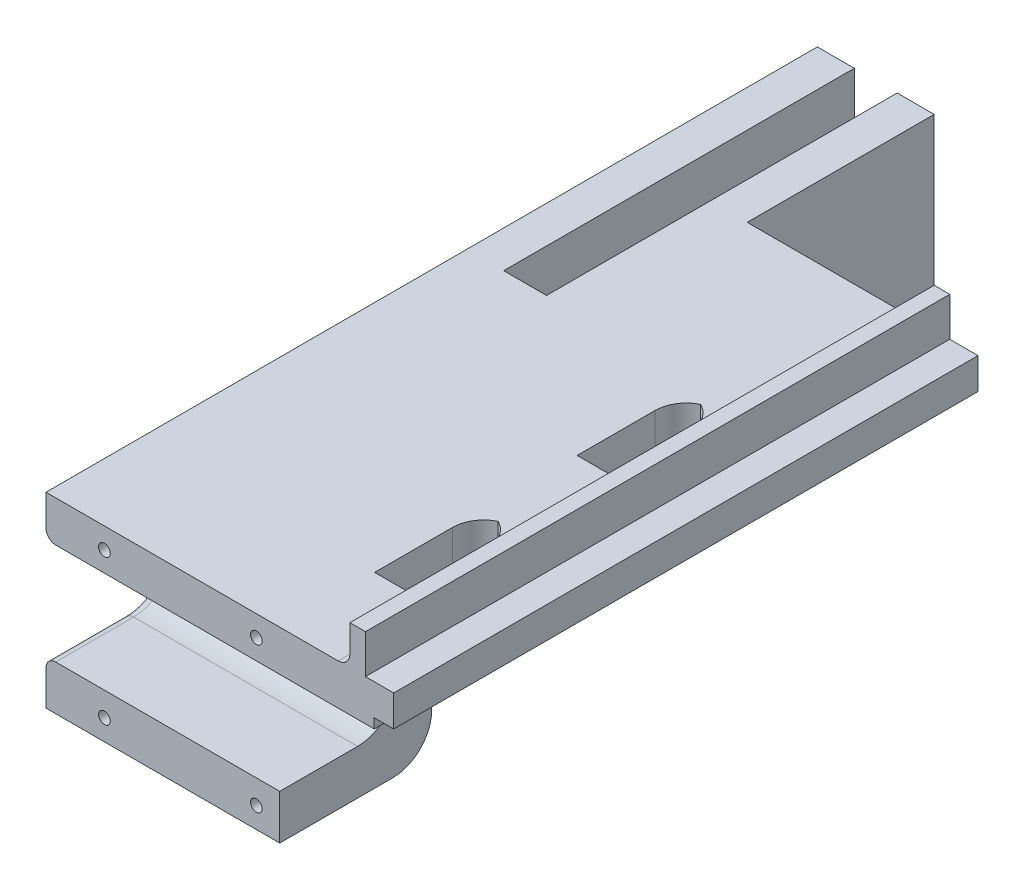
SolidWorks part; units mm, degrees
ref_plane "Alzado" through (0, 0, 0) normal (0, 0, 1) x (1, 0, 0)
ref_plane "Planta" through (0, 0, 0) normal (0, 1, 0) x (1, 0, 0)
ref_plane "Vista lateral" through (0, 0, 0) normal (1, 0, 0) x (0, 0, -1)
sketch "Croquis1" plane through (0, 0, 0) normal (0, 0, 1) x (1, 0, 0)
  line L1 (-66.2162, 31.0113) -> (-6.2162, 31.0113)
  line L2 (-66.2162, 31.0113) -> (-66.2162, -16.9887)
  line L3 (-66.2162, -16.9887) -> (-6.2162, -16.9887)
  line L4 (-6.2162, 31.0113) -> (-6.2162, -16.9887)
  dimension "D1" = 48
  dimension "D2" = 60
extrude "Saliente-Extruir1" add sketch "Croquis1" along normal blind 6
sketch "Croquis4" plane through (0, 0, 6) normal (0, 0, 1) x (1, 0, 0)
  line L0 (-66.2162, 31.0113) -> (-66.2162, 19.5113)
  line L1 (-66.2162, 31.0113) -> (-66.2162, -16.9887) construction
  line L3 (-66.2162, -5.4887) -> (-66.2162, -16.9887)
  line L4 (-66.2162, 31.0113) -> (-6.2162, 31.0113)
  line L6 (-6.2162, 31.0113) -> (-6.2162, 19.5113)
  line L7 (-6.2162, -16.9887) -> (-6.2162, 31.0113) construction
  line L8 (-6.2162, 19.5113) -> (-66.2162, 19.5113)
  line L9 (-66.2162, -5.4887) -> (-6.2162, -5.4887)
  line L10 (-6.2162, -5.4887) -> (-6.2162, -16.9887)
  line L11 (-6.2162, -16.9887) -> (-66.2162, -16.9887)
  dimension "D1" = 25
extrude "Saliente-Extruir3" add sketch "Croquis4" along normal blind 30
sketch "Croquis3" plane through (0, 0, 6) normal (0, 0, 1) x (1, 0, 0)
  circle A0 centre (-51.2162, 25.6613) radius 2.125
  circle A1 centre (-12.2162, 25.6613) radius 2.125
  circle A2 centre (-12.2162, -11.6387) radius 2.125
  circle A3 centre (-51.2162, -11.6387) radius 2.125
  dimension "D7" = 4.25
  dimension "D9" = 4.25
  dimension "D10" = 4.25
  dimension "D2" = 4.25
  dimension "D3" = 37.3
  dimension "D4" = 39
sketch "Croquis5" plane through (0, 0, 36) normal (0, 0, 1) x (1, 0, 0)
  circle A0 centre (-51.2162, 25.6613) radius 1.5
  circle A1 centre (-12.2162, 25.6613) radius 1.5
  circle A2 centre (-12.2162, -11.6387) radius 1.5
  circle A3 centre (-51.2162, -11.6387) radius 1.5
  dimension "D1" = 3
  dimension "D2" = 3
  dimension "D3" = 3
  dimension "D4" = 3
extrude "Cortar-Extruir3" cut sketch "Croquis5" against normal blind 16
sketch "Croquis6" plane through (0, 0, 0) normal (0, 0, -1) x (-1, 0, 0)
  line L0 (66.2162, -16.9887) -> (6.2162, -16.9887) construction
  line L1 (66.2162, 31.0113) -> (36.2162, 31.0113)
  line L2 (66.2162, 31.0113) -> (66.2162, -16.9887)
  line L3 (66.2162, -16.9887) -> (36.2162, -16.9887)
  line L4 (36.2162, 31.0113) -> (36.2162, -16.9887)
  dimension "D1" = 30
extrude "Saliente-Extruir4" add sketch "Croquis6" along normal blind 162
sketch "Croquis7" plane through (0, 0, -162) normal (0, 0, -1) x (-1, 0, 0)
  circle A0 centre (51.2162, 7.0113) radius 2
  dimension "D1" = 4
extrude "Cortar-Extruir4" cut sketch "Croquis7" against normal blind 16
sketch "Croquis8" plane through (0, 0, -162) normal (0, 0, -1) x (-1, 0, 0)
  line L0 (41.2162, 12.0113) -> (41.2162, 9.5131)
  line L10 (36.2162, 12.0113) -> (41.2162, 12.0113)
  line L11 (36.2162, 12.0113) -> (36.2162, 2.0113)
  line L12 (36.2162, 2.0113) -> (41.2162, 2.0113)
  line L21 (41.2162, 9.5131) -> (44.2162, 9.5131)
  line L23 (41.2162, 4.5131) -> (44.2162, 4.5131)
  line L24 (44.2162, 9.5131) -> (44.2162, 4.5131)
  line L25 (41.2162, 2.0113) -> (41.2162, 4.5131)
  dimension "D1" = 5
  dimension "D2" = 3
  dimension "D3" = 5
sketch "Croquis11" plane through (-36.2162, 0, 0) normal (1, 0, 0) x (0, 0, -1)
  line L1 (-36, 19.5113) -> (-36, 31.0113) construction
  line L4 (-36, 19.5113) -> (-36, 31.0113)
  line L6 (-36, 19.5113) -> (114, 19.5113)
  line L7 (114, 19.5113) -> (114, 31.0113)
  line L8 (162, 31.0113) -> (0, 31.0113) construction
  line L9 (162, 31.0113) -> (0, 31.0113) construction
  line L10 (-36, 31.0113) -> (114, 31.0113)
  dimension "D1" = 150
extrude "Saliente-Extruir6" add sketch "Croquis11" along normal blind 59.25
sketch "Croquis12" plane through (0, 31.0113, 0) normal (0, 1, 0) x (1, 0, 0)
  line L0 (23.0338, -36) -> (-66.2162, -36) construction
  line L1 (15.7838, -36) -> (11.7838, -36)
  line L2 (-66.2162, -36) -> (-66.2162, 162) construction
  line L3 (-66.2162, -36) -> (-66.2162, 162) construction
  line L4 (15.7838, -36) -> (15.7838, 114)
  line L5 (15.7838, 114) -> (11.7838, 114)
  line L6 (23.0338, 114) -> (-36.2162, 114) construction
  line L7 (11.7838, 114) -> (11.7838, -36)
  dimension "D1" = 82
  dimension "D2" = 150
  dimension "D3" = 4
extrude "Saliente-Extruir7" add sketch "Croquis12" along normal blind 10
sketch "Croquis14" plane through (0, 0, -114) normal (0, 0, -1) x (-1, 0, 0)
  line L0 (-23.0338, 23.0113) -> (-18.0338, 23.0113)
  line L1 (-18.0338, 23.0113) -> (-18.0338, 19.5113)
  line L2 (-23.0338, 23.0113) -> (-23.0338, 19.5113)
  line L3 (-23.0338, 19.5113) -> (-18.0338, 19.5113)
  line L4 (36.2162, 19.5113) -> (36.2162, 31.0113)
  line L5 (36.2162, 31.0113) -> (-11.7838, 31.0113)
  line L6 (-23.0338, 31.0113) -> (-23.0338, 19.5113)
  line L7 (-23.0338, 19.5113) -> (36.2162, 19.5113)
  line L8 (36.2162, 19.5113) -> (36.2162, 31.0113) construction
  line L9 (36.2162, 31.0113) -> (-11.7838, 31.0113) construction
  line L10 (-23.0338, 31.0113) -> (-23.0338, 19.5113) construction
  line L11 (-23.0338, 19.5113) -> (36.2162, 19.5113) construction
  line L20 (-11.7838, 31.0113) -> (-11.7838, 41.0113)
  line L22 (-11.7838, 41.0113) -> (-15.7838, 41.0113)
  line L24 (-15.7838, 41.0113) -> (-15.7838, 31.0113)
  line L26 (-15.7838, 31.0113) -> (-23.0338, 31.0113)
  line L27 (-15.7838, 31.0113) -> (-23.0338, 31.0113) construction
  dimension "D2" = 5
  dimension "D3" = 8
  dimension "D1" = 0
extrude "Cortar-Extruir6" cut sketch "Croquis14" against normal through all both and the other way through all
sketch "Croquis15" plane through (0, 0, -162) normal (0, 0, -1) x (-1, 0, 0)
  line L0 (51.2162, 45.0729) -> (51.2162, 16.9496) construction
  line L1 (56.7162, 20.0113) -> (45.7162, 20.0113)
  line L2 (45.7162, 20.0113) -> (45.7162, 31.0113)
  line L3 (56.7162, 20.0113) -> (56.7162, 31.0113)
  line L4 (66.2162, -16.9887) -> (66.2162, 31.0113)
  line L5 (66.2162, 31.0113) -> (36.2162, 31.0113)
  line L6 (36.2162, 31.0113) -> (36.2162, -16.9887)
  line L7 (36.2162, -16.9887) -> (66.2162, -16.9887)
  line L8 (66.2162, -16.9887) -> (66.2162, 31.0113) construction
  line L9 (66.2162, 31.0113) -> (36.2162, 31.0113) construction
  line L10 (56.7162, 31.0113) -> (45.7162, 31.0113)
  point P6 (51.2162, 31.0113)
  point P10 (51.2162, 20.0113)
  dimension "D2" = 11
  dimension "D3" = 11
  dimension "D1" = 0
extrude "Cortar-Extruir7" cut sketch "Croquis15" against normal blind 90 and the other way through all
sketch "Croquis16" plane through (-66.2162, 0, 0) normal (-1, 0, 0) x (0, 0, 1)
  line L0 (6, 19.5113) -> (6, 20.5113)
  line L1 (6, 20.5113) -> (36, 20.5113)
  line L2 (36, 31.0113) -> (36, 19.5113) construction
  line L3 (6, 19.5113) -> (36, 19.5113)
  line L4 (36, 19.5113) -> (36, 20.5113)
  dimension "D1" = 1
extrude "Cortar-Extruir10" cut sketch "Croquis16" against normal through all contours L1 L4 L3 L0
fillet "Redondeo1" radius 10 2 edges at (-36.2162, -5.4887, 6) (-24.0912, 20.5113, 6)
sketch "Croquis20" plane through (0, 0, 0) normal (0, 0, -1) x (-1, 0, 0)
  line L1 (6.2162, 19.5113) -> (36.2162, 19.5113)
  line L2 (6.2162, 19.5113) -> (6.2162, -16.9887)
  line L3 (6.2162, -16.9887) -> (36.2162, -16.9887)
  line L4 (36.2162, 19.5113) -> (36.2162, -16.9887)
extrude "Saliente-Extruir8" add sketch "Croquis20" along normal blind 50
sketch "Croquis21" plane through (0, 19.5113, 0) normal (0, -1, 0) x (1, 0, 0)
  line L1 (2.7838, 11.6411) -> (-6.2162, 11.6411)
  line L2 (2.7838, 11.6411) -> (2.7838, -16.3589)
  line L3 (2.7838, -16.3589) -> (-6.2162, -16.3589)
  line L4 (-6.2162, 11.6411) -> (-6.2162, -16.3589)
  line L5 (18.0338, 11.6411) -> (-6.2162, 11.6411) construction
  line L6 (-6.2162, 36) -> (-6.2162, -50) construction
  line L12 (-1.7162, 20.4456) -> (-1.7162, -78.1671) construction
  line L13 (2.7838, -40.3589) -> (2.7838, -68.3589)
  line L14 (2.7838, -40.3589) -> (-6.2162, -40.3589)
  line L15 (-6.2162, -40.3589) -> (-6.2162, -68.3589)
  line L16 (2.7838, -68.3589) -> (-6.2162, -68.3589)
  point P10 (-1.7162, -16.3589)
  dimension "D1" = 9
  dimension "D2" = 28
  dimension "D3" = 2
  dimension "D4" = 24
extrude "Cortar-Extruir11" cut sketch "Croquis21" against normal blind 40
sketch "Croquis22" plane through (0, 0, -50) normal (0, 0, -1) x (-1, 0, 0)
  line L1 (36.2162, 19.5113) -> (6.2162, 19.5113)
  line L2 (36.2162, 19.5113) -> (36.2162, -16.9887)
  line L3 (36.2162, -16.9887) -> (6.2162, -16.9887)
  line L4 (6.2162, 19.5113) -> (6.2162, -16.9887)
extrude "Cortar-Extruir13" cut sketch "Croquis22" against normal blind 47
fillet "Redondeo3" radius 10 1 edges at (-21.2162, -16.9887, -3)
sketch "Croquis23" plane through (0, 0, 36) normal (0, 0, 1) x (1, 0, 0)
  circle A0 centre (-12.2162, -11.6387) radius 1.5 construction
  circle A1 centre (-51.2162, -11.6387) radius 1.5 construction
  circle A2 centre (-12.2162, 25.6613) radius 1.5 construction
  circle A3 centre (-51.2162, 25.6613) radius 1.5 construction
  circle A4 centre (-12.2162, -11.6387) radius 1.5
  circle A5 centre (-51.2162, -11.6387) radius 1.5
  circle A6 centre (-12.2162, 25.6613) radius 1.5
  circle A7 centre (-51.2162, 25.6613) radius 1.5
extrude "Cortar-Extruir14" cut sketch "Croquis23" against normal blind 16
fillet "Redondeo4" radius 3 1 edges at (11.7838, 31.0113, -39)
sketch "Croquis24" plane through (0, 0, -162) normal (0, 0, -1) x (-1, 0, 0)
  line L0 (36.2162, -16.9887) -> (66.2162, -16.9887) construction
  line L1 (36.2162, -16.9887) -> (66.2162, -16.9887) construction
  line L2 (51.2162, 1.6971) -> (51.2162, -35.6746) construction
  line L3 (48.6162, -16.9887) -> (48.6162, -12.9887)
  line L4 (48.6162, -12.9887) -> (44.2162, -12.9887)
  line L5 (44.2162, -12.9887) -> (44.2162, -8.9887)
  line L6 (44.2162, -8.9887) -> (58.2162, -8.9887)
  line L7 (48.6162, -16.9887) -> (53.8162, -16.9887)
  line L8 (58.2162, -12.9887) -> (58.2162, -8.9887)
  line L9 (53.8162, -12.9887) -> (58.2162, -12.9887)
  line L10 (53.8162, -16.9887) -> (53.8162, -12.9887)
  point P5 (51.2162, -16.9887)
  point P12 (51.2162, -16.9887)
  point P13 (51.2162, -8.9887)
  dimension "D1" = 4
  dimension "D2" = 4
  dimension "D3" = 7
  dimension "D4" = 2.6
extrude "Cortar-Extruir15" cut sketch "Croquis24" against normal blind 170
fillet "Redondeo5" radius 6 1 edges at (-36.2162, 19.5113, -58.5)
fillet "Redondeo6" radius 2.5 5 edges at (-66.2162, 20.5113, 26) (-66.2162, 17.5823, 8.9289) (-66.2162, 7.5113, 6) (-66.2162, -2.5598, 8.9289) (-66.2162, -5.4887, 26)
fillet "Redondeo7" radius 8 4 edges at (2.7838, 25.2613, -68.3589) (-6.2162, 25.2613, -68.3589) (-6.2162, 25.2613, -16.3589) (2.7838, 25.2613, -16.3589)
